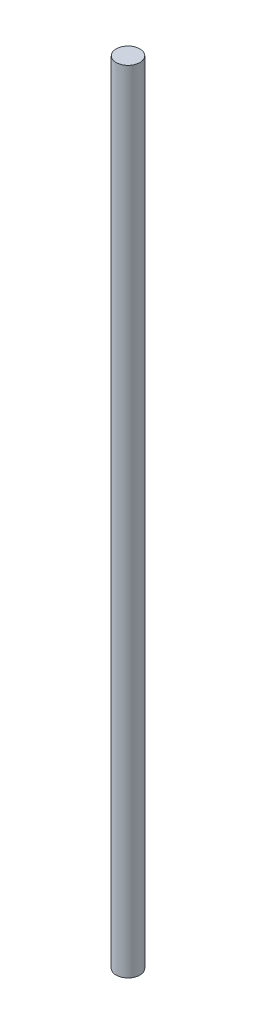
SolidWorks part; units mm, degrees
material "6061 Alloy"
ref_plane "Front Plane" through (0, 0, 0) normal (0, 0, 1) x (1, 0, 0)
ref_plane "Top Plane" through (0, 0, 0) normal (0, 1, 0) x (1, 0, 0)
ref_plane "Right Plane" through (0, 0, 0) normal (1, 0, 0) x (0, 0, -1)
sketch "Sketch1" plane through (0, 0, 0) normal (0, 1, 0) x (1, 0, 0)
  circle A0 centre (0, 0) radius 3
  dimension "Diam" = 6
extrude "Boss-Extrude1" add sketch "Sketch1" along normal mid plane 200
ref_axis "Axis1" through (0, 100, 0) along (0, -1, 0)
